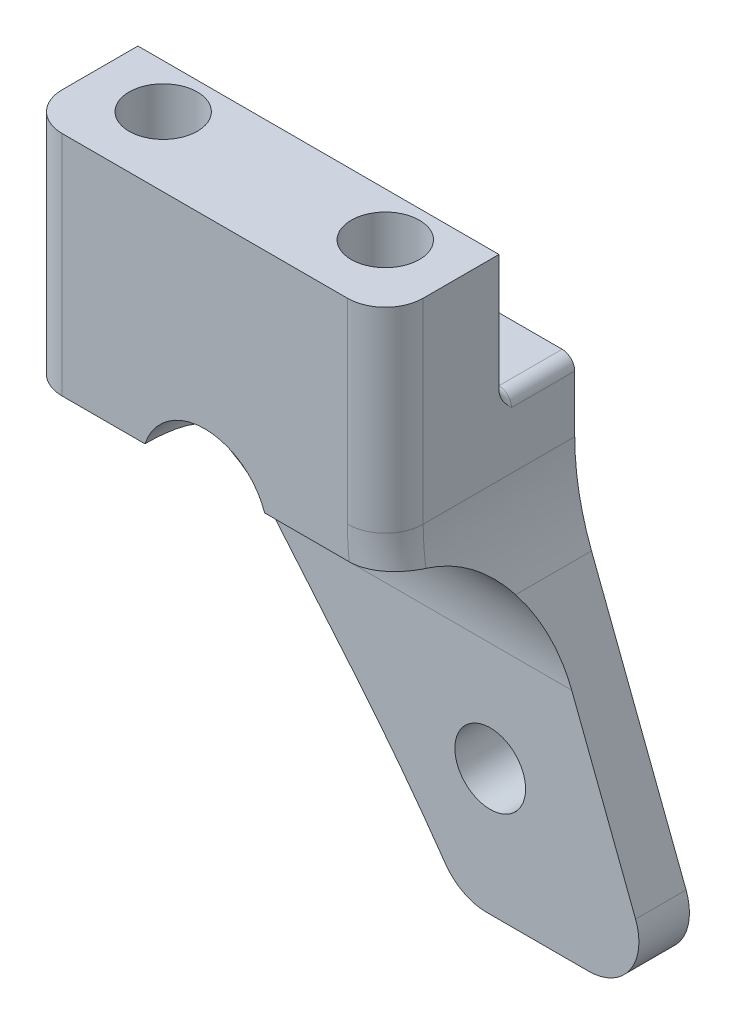
SolidWorks part; units mm, degrees
material "尼龙 101"
ref_plane "前视基准面" through (0, 0, 0) normal (0, 0, 1) x (1, 0, 0)
ref_plane "上视基准面" through (0, 0, 0) normal (0, 1, 0) x (1, 0, 0)
ref_plane "右视基准面" through (0, 0, 0) normal (1, 0, 0) x (0, 0, -1)
sketch "草图2" plane through (0, 0, 0) normal (0, 0, 1) x (1, 0, 0)
  line L0 (99.684, -6.6313) -> (103.4274, -16.3833)
  line L1 (97.5389, -19.1) -> (101.5602, -19.1)
  line L7 (98.5198, -0.3) -> (85.228, -0.3)
  line L8 (84.728, -0.8) -> (84.728, -3.0477)
  line L9 (85.6639, -5.6188) -> (92.239, -13.4548)
  line L10 (103.2964, -32.2265) -> (113.4297, -58.6246)
  line L11 (110.914, -75) -> (116.4707, -75)
  line L12 (122.539, -66.1706) -> (99.684, -6.6313)
  line L13 (99.0198, -3.0477) -> (99.0198, -0.8)
  line L14 (98.5198, -0.3) -> (85.228, -0.3)
  line L15 (84.728, -0.8) -> (84.728, -3.0477)
  line L16 (85.6639, -5.6188) -> (92.239, -13.4548)
  line L17 (103.2964, -32.2265) -> (113.4297, -58.6246) construction
  line L18 (110.914, -75) -> (116.4707, -75) construction
  line L19 (122.539, -66.1706) -> (99.684, -6.6313) construction
  line L20 (99.0198, -3.0477) -> (99.0198, -0.8)
  circle A0 centre (97.6739, -14.1) radius 1.4 construction
  circle A1 centre (91.8739, -5.1) radius 1.4 construction
  circle A2 centre (97.6739, -14.1) radius 1.4
  circle A3 centre (91.8739, -5.1) radius 1.4
  arc A4 (92.239, -13.4548) -> (95.896, -18.2406) centre (41.6801, -55.8787) cw
  arc A5 (101.5602, -19.1) -> (103.4274, -16.3833) centre (101.5602, -17.1) ccw
  arc A6 (95.896, -18.2406) -> (97.5389, -19.1) centre (97.5389, -17.1) ccw
  arc A9 (85.228, -0.3) -> (84.728, -0.8) centre (85.228, -0.8) ccw
  arc A10 (84.728, -3.0477) -> (85.6639, -5.6188) centre (88.728, -3.0477) ccw
  arc A11 (103.2964, -32.2265) -> (92.239, -13.4548) centre (41.6801, -55.8787) ccw
  arc A12 (111.7471, -64.1882) -> (113.4297, -58.6246) centre (109.0055, -60.3229) ccw
  arc A13 (111.7471, -64.1882) -> (108.4959, -73.1348) centre (116.5864, -71.0109) ccw
  arc A14 (108.4959, -73.1348) -> (110.914, -75) centre (110.914, -72.5) ccw
  arc A15 (116.4707, -75) -> (122.539, -66.1706) centre (116.4707, -68.5) ccw
  arc A16 (99.0198, -3.0477) -> (99.684, -6.6313) centre (109.0198, -3.0477) ccw
  arc A17 (99.0198, -0.8) -> (98.5198, -0.3) centre (98.5198, -0.8) ccw
  arc A18 (85.228, -0.3) -> (84.728, -0.8) centre (85.228, -0.8) ccw
  arc A19 (84.728, -3.0477) -> (85.6639, -5.6188) centre (88.728, -3.0477) ccw
  arc A20 (103.2964, -32.2265) -> (92.239, -13.4548) centre (41.6801, -55.8787) ccw construction
  arc A21 (111.7471, -64.1882) -> (113.4297, -58.6246) centre (109.0055, -60.3229) ccw construction
  arc A22 (111.7471, -64.1882) -> (108.4959, -73.1348) centre (116.5864, -71.0109) ccw construction
  arc A23 (108.4959, -73.1348) -> (110.914, -75) centre (110.914, -72.5) ccw construction
  arc A24 (116.4707, -75) -> (122.539, -66.1706) centre (116.4707, -68.5) ccw construction
  arc A25 (99.0198, -3.0477) -> (99.684, -6.6313) centre (109.0198, -3.0477) ccw
  arc A26 (99.0198, -0.8) -> (98.5198, -0.3) centre (98.5198, -0.8) ccw
  point P38 (104.4702, -19.1)
  point P41 (96.4827, -19.1)
  dimension "D3" = 2
  dimension "D4" = 2
  dimension "D2" = 5
  dimension "D1" = 0
extrude "凸台-拉伸1" add sketch "草图2" along normal blind 2
sketch "草图3" plane through (0, 0, 2) normal (0, 0, 1) x (1, 0, 0)
  line L2 (99.0985, -4.3) -> (84.9291, -4.3)
  line L6 (98.5198, -0.3) -> (85.228, -0.3)
  line L7 (84.728, -0.8) -> (84.728, -3.0477)
  line L8 (85.6639, -5.6188) -> (92.239, -13.4548)
  line L9 (97.5389, -19.1) -> (101.5602, -19.1)
  line L10 (103.4274, -16.3833) -> (99.684, -6.6313)
  line L11 (99.0198, -3.0477) -> (99.0198, -0.8)
  line L12 (98.5198, -0.3) -> (85.228, -0.3)
  line L13 (84.728, -0.8) -> (84.728, -3.0477)
  line L14 (85.6639, -5.6188) -> (92.239, -13.4548) construction
  line L15 (97.5389, -19.1) -> (101.5602, -19.1) construction
  line L16 (103.4274, -16.3833) -> (99.684, -6.6313) construction
  line L17 (99.0198, -3.0477) -> (99.0198, -0.8)
  arc A1 (84.728, -3.0477) -> (85.6639, -5.6188) centre (88.728, -3.0477) ccw construction
  arc A2 (84.728, -3.0477) -> (84.9291, -4.3) centre (88.728, -3.0477) ccw
  arc A3 (99.0198, -3.0477) -> (99.684, -6.6313) centre (109.0198, -3.0477) ccw construction
  arc A4 (99.0198, -3.0477) -> (99.0985, -4.3) centre (109.0198, -3.0477) ccw
  arc A7 (99.0198, -0.8) -> (98.5198, -0.3) centre (98.5198, -0.8) ccw
  arc A8 (85.228, -0.3) -> (84.728, -0.8) centre (85.228, -0.8) ccw
  arc A9 (84.728, -3.0477) -> (85.6639, -5.6188) centre (88.728, -3.0477) ccw
  arc A10 (95.896, -18.2406) -> (92.239, -13.4548) centre (41.6801, -55.8787) ccw
  arc A11 (95.896, -18.2406) -> (97.5389, -19.1) centre (97.5389, -17.1) ccw
  arc A12 (101.5602, -19.1) -> (103.4274, -16.3833) centre (101.5602, -17.1) ccw
  arc A13 (99.0198, -3.0477) -> (99.684, -6.6313) centre (109.0198, -3.0477) ccw
  arc A14 (99.0198, -0.8) -> (98.5198, -0.3) centre (98.5198, -0.8) ccw
  arc A15 (85.228, -0.3) -> (84.728, -0.8) centre (85.228, -0.8) ccw
  arc A16 (84.728, -3.0477) -> (85.6639, -5.6188) centre (88.728, -3.0477) ccw construction
  arc A17 (95.896, -18.2406) -> (92.239, -13.4548) centre (41.6801, -55.8787) ccw construction
  arc A18 (95.896, -18.2406) -> (97.5389, -19.1) centre (97.5389, -17.1) ccw construction
  arc A19 (101.5602, -19.1) -> (103.4274, -16.3833) centre (101.5602, -17.1) ccw construction
  dimension "D2" = 4
  dimension "D1" = 0
extrude "凸台-拉伸2" add sketch "草图3" along normal blind 5.5
sketch "草图4" plane through (0, 0, 2) normal (0, 0, 1) x (1, 0, 0)
  circle A0 centre (91.8739, -5.1) radius 1.4
extrude "切除-拉伸1" cut sketch "草图4" against normal through all both and the other way through all
fillet "圆角2" radius 5.5 1 edges at (96.0607, -4.3, 2)
sketch "草图5" plane through (0, 0, 7.5) normal (0, 0, 1) x (1, 0, 0)
  circle A0 centre (91.8739, -5.1) radius 2.5
  arc A1 (93.0228, -4.3) -> (90.725, -4.3) centre (91.8739, -5.1) ccw construction
  dimension "D1" = 5
extrude "切除-拉伸2" cut sketch "草图5" against normal up to surface (5.5 mm away) up to face at (97.3425, -15.2186, 2)
sketch "草图7" plane through (0, -0.3, 0) normal (0, 1, 0) x (1, 0, 0)
  line L0 (98.5198, -7.5) -> (85.228, -7.5) construction
  line L2 (99.0198, -7.5) -> (99.0198, 0) construction
  line L4 (89.5054, -7.5) -> (94.2424, -7.5) construction
  line L5 (84.728, -7.5) -> (84.728, 0) construction
  circle A0 centre (96.2698, -4.75) radius 2.75 construction
  circle A1 centre (96.2698, -4.75) radius 1.35
  circle A2 centre (87.478, -4.75) radius 2.75 construction
  circle A3 centre (87.478, -4.75) radius 1.35
  dimension "D1" = 5.5
  dimension "D2" = 2.7
extrude "切除-拉伸3" cut sketch "草图7" against normal through all both and the other way through all
ref_plane "基准面1" through (0, -4.3, 0) normal (0, 1, 0) x (1, 0, 0)
sketch "草图8" plane through (0, -4.3, 0) normal (0, 1, 0) x (1, 0, 0)
  circle A4 centre (98.8741, -7.2966) radius 0.1223
extrude "切除-拉伸4" cut sketch "草图8" against normal through all
fillet "圆角3" radius 1.5 3 edges at (84.728, -1.9238, 7.5) (99.0395, -3.6751, 7.5) (99.0198, -1.9238, 7.5) tangent propagation no
sketch "草图10" plane through (0, -0.3, 0) normal (0, 1, 0) x (1, 0, 0)
  line L0 (99.0198, -6) -> (99.0198, 0) construction
  line L1 (99.0198, -6) -> (99.0198, 0) construction
  line L2 (97.5198, -7.5) -> (86.228, -7.5) construction
  line L3 (97.5198, -7.5) -> (86.228, -7.5)
  line L4 (84.728, -6) -> (84.728, 0) construction
  line L5 (84.728, -6) -> (84.728, 0) construction
  line L6 (99.0198, -3) -> (84.728, -3)
  line L7 (79.066, -3) -> (37.1742, -3) construction
  line L8 (99.0198, -3) -> (99.0198, -6)
  line L9 (84.728, -3) -> (84.728, -6)
  arc A0 (97.5198, -7.5) -> (99.0198, -6) centre (97.5198, -6) ccw construction
  arc A1 (97.5198, -7.5) -> (99.0198, -6) centre (97.5198, -6) ccw
  arc A2 (85.228, -7.118) -> (86.228, -7.5) centre (86.228, -6) ccw construction
  arc A3 (85.228, -7.118) -> (86.228, -7.5) centre (86.228, -6) ccw
  arc A4 (84.728, -6) -> (85.228, -7.118) centre (86.228, -6) ccw construction
  arc A5 (84.728, -6) -> (85.228, -7.118) centre (86.228, -6) ccw
  circle A6 centre (96.2698, -4.75) radius 1.35 construction
  circle A7 centre (96.2698, -4.75) radius 1.35
  circle A8 centre (87.478, -4.75) radius 1.35 construction
  circle A9 centre (87.478, -4.75) radius 1.35
extrude "凸台-拉伸3" add sketch "草图10" along normal blind 5 and the other way blind 1
fillet "圆角4" radius 0.5 3 edges at (84.8745, -0.4464, 3) (91.8739, -0.3, 3) (98.8733, -0.4464, 3)
